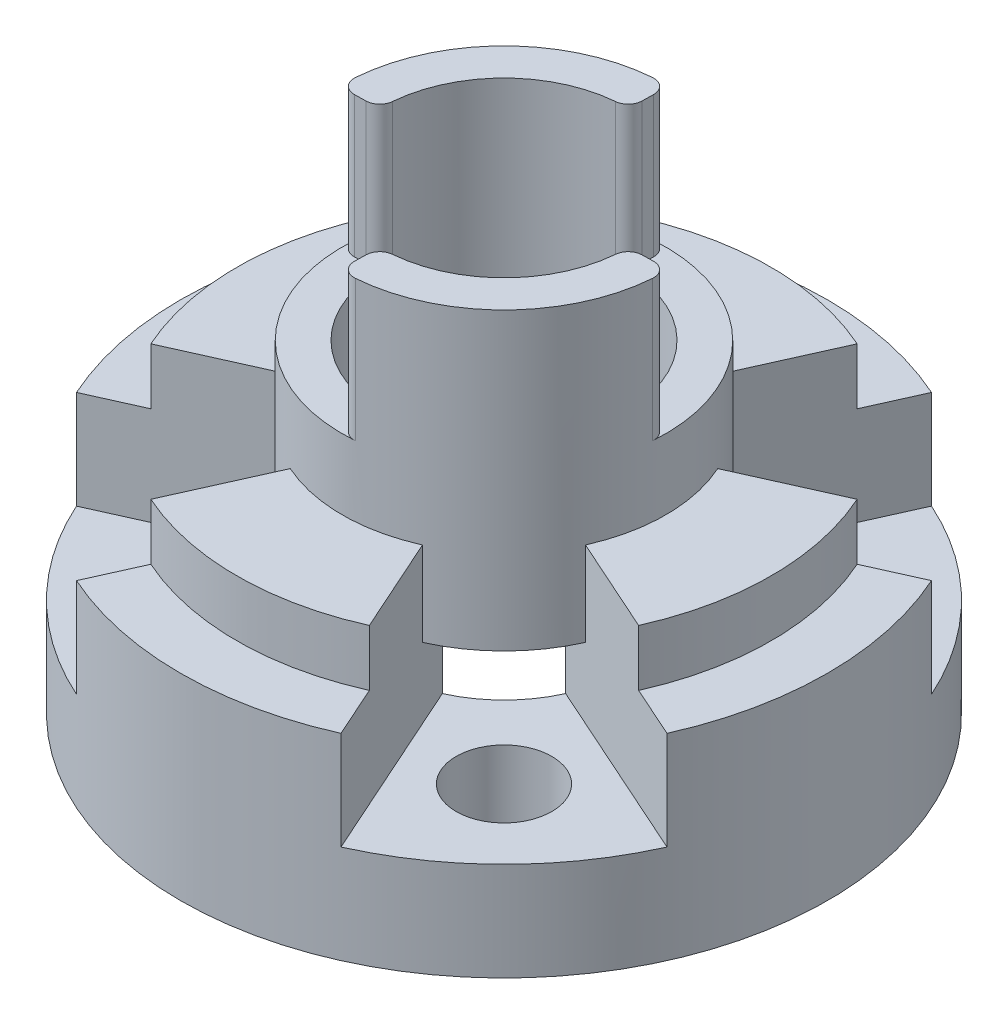
SolidWorks part; units mm, degrees
ref_plane "Alzado" through (0, 0, 0) normal (0, 0, 1) x (1, 0, 0)
ref_plane "Planta" through (0, 0, 0) normal (0, 1, 0) x (1, 0, 0)
ref_plane "Vista lateral" through (0, 0, 0) normal (1, 0, 0) x (0, 0, -1)
sketch "Croquis1" plane through (0, 0, 0) normal (0, 1, 0) x (1, 0, 0)
  line L0 (-8.3, -8.3) -> (8.3, 8.3) construction
  line L1 (-8.3, 8.3) -> (8.3, -8.3) construction
  circle A0 centre (0, 0) radius 4.35
  circle A1 centre (5.6569, 5.6569) radius 1.7
  circle A2 centre (-5.6569, 5.6569) radius 1.7
  circle A3 centre (-5.6569, -5.6569) radius 1.7
  circle A4 centre (5.6569, -5.6569) radius 1.7
  circle A5 centre (0, 0) radius 11.5
  dimension "D1" = 8.7
  dimension "D2" = 23
  dimension "D3" = 3.4
  dimension "D4" = 3.4
  dimension "D5" = 3.4
  dimension "D6" = 3.4
extrude "Saliente-Extruir1" add sketch "Croquis1" along normal blind 3.5
sketch "Croquis2" plane through (0, 3.5, 0) normal (0, 1, 0) x (1, 0, 0)
  circle A0 centre (0, 0) radius 4.35 construction
  circle A1 centre (0, 0) radius 4.35
  circle A2 centre (0, 0) radius 5.75
  dimension "D1" = 1.4
extrude "Saliente-Extruir2" add sketch "Croquis2" along normal blind 13
sketch "Croquis3" plane through (0, 16.5, 0) normal (0, 1, 0) x (1, 0, 0)
  line L0 (0, 0) -> (-0.1004, -5.7491) construction
  line L1 (-5.7491, -0.1004) -> (-4.3493, -0.0759)
  line L2 (5.7491, 0.1004) -> (4.3493, 0.0759)
  line L3 (-0.1004, -5.7491) -> (-0.0759, -4.3493)
  line L4 (0.1004, 5.7491) -> (0.0759, 4.3493)
  line L6 (0, 0) -> (-5.6569, -5.6569) construction
  circle A0 centre (0, 0) radius 5.75 construction
  circle A1 centre (0, 0) radius 4.35 construction
  arc A2 (-4.3493, -0.0759) -> (-0.0759, -4.3493) centre (0, 0) ccw
  arc A3 (-5.7491, -0.1004) -> (-0.1004, -5.7491) centre (0, 0) ccw
  circle A4 centre (0, 0) radius 5.75 construction
  arc A5 (5.7491, 0.1004) -> (0.1004, 5.7491) centre (0, 0) ccw
  arc A6 (4.3493, 0.0759) -> (0.0759, 4.3493) centre (0, 0) ccw
  point P21 (0, 0)
  dimension "D1" = 2
  dimension "D2" = 44
extrude "Cortar-Extruir1" cut sketch "Croquis3" against normal blind 5
sketch "Croquis4" plane through (0, 0, 0) normal (0, -1, 0) x (1, 0, 0)
  circle A0 centre (0, 0) radius 4.35 construction
  circle A1 centre (0, 0) radius 4.35
  circle A2 centre (0, 0) radius 5.275
  dimension "D1" = 10.55
extrude "Cortar-Extruir2" cut sketch "Croquis4" against normal blind 2
fillet "Redondeo1" radius 0.6 1 edges at (0, 0, -5.275)
fillet "Redondeo2" radius 0.5 8 edges at (4.3493, 14, -0.0759) (5.7491, 14, -0.1004) (-0.0759, 14, 4.3493) (-0.1004, 14, 5.7491) (0.1004, 14, -5.7491) (0.0759, 14, -4.3493) (-4.3493, 14, 0.0759) (-5.7491, 14, 0.1004)
sketch "Croquis5" plane through (0, 3.5, 0) normal (0, 1, 0) x (1, 0, 0)
  line L0 (10.4951, 4.7013) -> (5.2476, 2.3506)
  line L1 (10.4951, -4.7013) -> (5.2476, -2.3506)
  line L2 (0, 0) -> (10.4951, -4.7013) construction
  line L3 (0, 0) -> (10.4951, 4.7013) construction
  line L4 (4.7013, -10.4951) -> (2.3506, -5.2476)
  line L5 (-4.7013, -10.4951) -> (-2.3506, -5.2476)
  line L6 (0, 0) -> (-4.7013, 10.4951) construction
  line L7 (0, 0) -> (4.7013, 10.4951) construction
  line L8 (0, 0) -> (-4.7013, -10.4951) construction
  line L9 (0, 0) -> (4.7013, -10.4951) construction
  line L10 (-4.7013, 10.4951) -> (-2.3506, 5.2476)
  line L11 (4.7013, 10.4951) -> (2.3506, 5.2476)
  line L12 (-10.4951, -4.7013) -> (-5.2476, -2.3506)
  line L13 (-10.4951, 4.7013) -> (-5.2476, 2.3506)
  line L14 (0, 0) -> (-10.4951, 4.7013) construction
  line L15 (0, 0) -> (-10.4951, -4.7013) construction
  arc A0 (4.7013, 10.4951) -> (-4.7013, 10.4951) centre (0, 0) ccw
  circle A1 centre (0, 0) radius 5.75 construction
  circle A2 centre (0, 0) radius 11.5 construction
  arc A3 (2.3506, 5.2476) -> (-2.3506, 5.2476) centre (0, 0) ccw
  arc A4 (5.2476, -2.3506) -> (5.2476, 2.3506) centre (0, 0) ccw
  circle A5 centre (-5.6569, 5.6569) radius 1.7 construction
  arc A6 (10.4951, -4.7013) -> (10.4951, 4.7013) centre (0, 0) ccw
  arc A7 (-2.3506, -5.2476) -> (2.3506, -5.2476) centre (0, 0) ccw
  circle A8 centre (5.6569, 5.6569) radius 1.7 construction
  arc A9 (-4.7013, -10.4951) -> (4.7013, -10.4951) centre (0, 0) ccw
  arc A10 (-5.2476, 2.3506) -> (-5.2476, -2.3506) centre (0, 0) ccw
  arc A11 (-10.4951, 4.7013) -> (-10.4951, -4.7013) centre (0, 0) ccw
  point P31 (0, 0)
  circle M11 centre (0, 0) radius 11.5
  circle M14 centre (0, 0) radius 5.75
  dimension "D1" = 4
  dimension "D5" = 2.85
  dimension "D6" = 2.85
extrude "Saliente-Extruir3" add sketch "Croquis5" along normal blind 3.5 contours M11 M14 | M11 M14 | M11 M14 | L11 L10 M11 M14 region at (8.6824, 3.5, 0) region at (0, 3.5, -8.6824) region at (0, 3.5, 8.6824) region at (-8.6824, 3.5, 0)
sketch "Croquis7" plane through (0, 7, 0) normal (0, 1, 0) x (1, 0, 0)
  line L0 (10.4951, 4.7013) -> (5.2476, 2.3506) construction
  line L1 (10.4951, -4.7013) -> (5.2476, -2.3506) construction
  line L2 (3.8837, -8.6699) -> (2.3506, -5.2476)
  line L3 (-2.3506, -5.2476) -> (-3.8837, -8.6699)
  line L4 (-8.6699, -3.8837) -> (-5.2476, -2.3506)
  line L5 (-5.2476, 2.3506) -> (-8.6699, 3.8837)
  line L6 (5.2476, -2.3506) -> (10.4951, -4.7013)
  line L7 (5.2476, -2.3506) -> (8.6699, -3.8837)
  line L8 (-3.8837, 8.6699) -> (-2.3506, 5.2476)
  line L9 (2.3506, 5.2476) -> (3.8837, 8.6699)
  line L14 (10.4951, 4.7013) -> (5.2476, 2.3506)
  line L15 (8.6699, 3.8837) -> (5.2476, 2.3506)
  arc A0 (8.6699, -3.8837) -> (8.6699, 3.8837) centre (0, 0) ccw
  arc A2 (10.4951, -4.7013) -> (10.4951, 4.7013) centre (0, 0) ccw construction
  arc A3 (-2.3506, -5.2476) -> (2.3506, -5.2476) centre (0, 0) ccw
  arc A4 (10.4951, -4.7013) -> (10.4951, 4.7013) centre (0, 0) ccw
  arc A5 (5.2476, -2.3506) -> (5.2476, 2.3506) centre (0, 0) ccw
  arc A6 (-3.8837, -8.6699) -> (3.8837, -8.6699) centre (0, 0) ccw
  arc A7 (5.2476, -2.3506) -> (5.2476, 2.3506) centre (0, 0) ccw
  arc A8 (-5.2476, 2.3506) -> (-5.2476, -2.3506) centre (0, 0) ccw
  arc A9 (-8.6699, 3.8837) -> (-8.6699, -3.8837) centre (0, 0) ccw
  arc A10 (2.3506, 5.2476) -> (-2.3506, 5.2476) centre (0, 0) ccw
  arc A11 (3.8837, 8.6699) -> (-3.8837, 8.6699) centre (0, 0) ccw
  point P30 (0, 0)
  point P34 (0, 0)
  arc M4 (5.2476, 2.3506) -> (5.2476, -2.3506) centre (0, 0) cw
  line M27 (5.2476, -2.3506) -> (10.4951, -4.7013)
  line M28 (10.4951, 4.7013) -> (5.2476, 2.3506)
  dimension "D1" = 2
  dimension "D3" = 4
  dimension "D2" = 0
extrude "Saliente-Extruir4" add sketch "Croquis7" along normal blind 2 contours L5 A9 L4 A8 | L9 A11 L8 A10 | A0 M27 M28 M4 | L3 A6 L2 A3 region at (0, 7, 7.5508) region at (-7.5508, 7, 0) region at (7.5508, 7, 0) region at (0, 7, -7.5508)
sketch "Croquis8" plane through (0, 3.5, 0) normal (0, 1, 0) x (1, 0, 0)
  line L0 (-5.2476, 2.3506) -> (-3.9699, 1.7783)
  line L1 (-2.3506, 5.2476) -> (-1.7783, 3.9699)
  line L2 (-4.7013, 10.4951) -> (-2.3506, 5.2476) construction
  line L4 (5.2476, 2.3506) -> (3.9699, 1.7783)
  line L5 (2.3506, 5.2476) -> (1.7783, 3.9699)
  line L6 (2.3506, -5.2476) -> (1.7783, -3.9699)
  line L7 (5.2476, -2.3506) -> (3.9699, -1.7783)
  line L8 (-5.2476, -2.3506) -> (-3.9699, -1.7783)
  line L9 (-2.3506, -5.2476) -> (-1.7783, -3.9699)
  arc A0 (-2.3506, 5.2476) -> (-5.2476, 2.3506) centre (0, 0) ccw construction
  arc A1 (-2.3506, 5.2476) -> (-5.2476, 2.3506) centre (0, 0) ccw
  arc A2 (-3.9699, 1.7783) -> (-1.7783, 3.9699) centre (0, 0) cw
  arc A3 (1.7783, 3.9699) -> (3.9699, 1.7783) centre (0, 0) cw
  arc A4 (5.2476, 2.3506) -> (2.3506, 5.2476) centre (0, 0) ccw
  circle A5 centre (0, 0) radius 4.35 construction
  arc A6 (3.9699, -1.7783) -> (1.7783, -3.9699) centre (0, 0) cw
  arc A7 (2.3506, -5.2476) -> (5.2476, -2.3506) centre (0, 0) ccw
  arc A8 (-1.7783, -3.9699) -> (-3.9699, -1.7783) centre (0, 0) cw
  arc A9 (-5.2476, -2.3506) -> (-2.3506, -5.2476) centre (0, 0) ccw
  point P17 (0, 0)
  point P27 (0, 0)
  dimension "D1" = 4
extrude "Cortar-Extruir3" cut sketch "Croquis8" along normal blind 2.5
